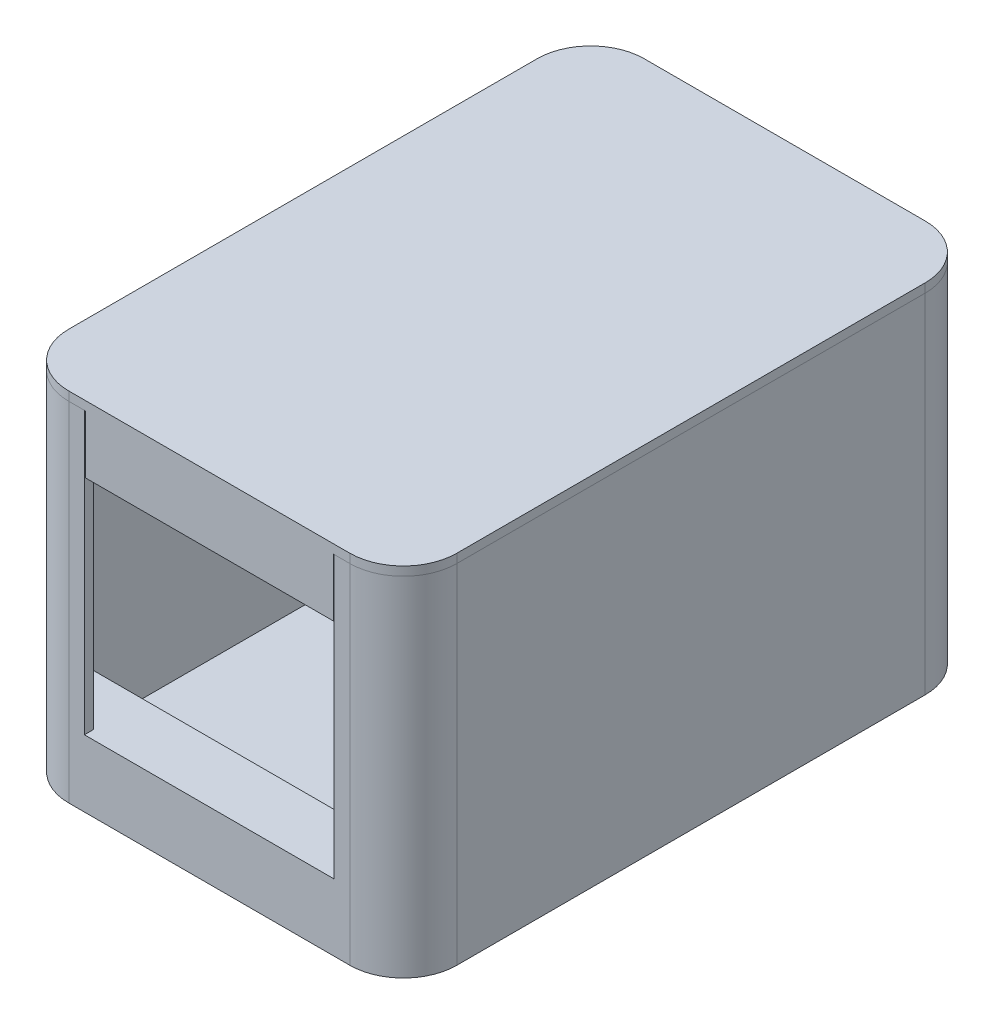
SolidWorks part; units mm, degrees
other "Cover"
other "Case"
ref_plane "Front Plane" through (0, 0, 0) normal (0, 0, 1) x (1, 0, 0)
ref_plane "Top Plane" through (0, 0, 0) normal (0, 1, 0) x (1, 0, 0)
ref_plane "Right Plane" through (0, 0, 0) normal (1, 0, 0) x (0, 0, -1)
sketch "Sketch1" plane through (0, 0, 0) normal (0, 1, 0) x (1, 0, 0)
  line L0 (43.5, 52.5) -> (43.5, -52.5)
  line L1 (-31.5, 62.5) -> (31.5, 62.5) construction
  line L2 (-41.5, 52.5) -> (-41.5, -52.5) construction
  line L3 (-31.5, -62.5) -> (31.5, -62.5) construction
  line L4 (41.5, 52.5) -> (41.5, -52.5) construction
  line L5 (-41.5, 62.5) -> (41.5, -62.5) construction
  line L6 (-41.5, -62.5) -> (41.5, 62.5) construction
  line L7 (-31.5, -64.5) -> (31.5, -64.5)
  line L8 (-43.5, 52.5) -> (-43.5, -52.5)
  line L9 (-31.5, 64.5) -> (31.5, 64.5)
  arc A0 (31.5, -62.5) -> (41.5, -52.5) centre (31.5, -52.5) ccw construction
  arc A1 (-41.5, -52.5) -> (-31.5, -62.5) centre (-31.5, -52.5) ccw construction
  arc A2 (-41.5, 52.5) -> (-31.5, 62.5) centre (-31.5, 52.5) cw construction
  arc A3 (41.5, 52.5) -> (31.5, 62.5) centre (31.5, 52.5) ccw construction
  arc A4 (31.5, -64.5) -> (43.5, -52.5) centre (31.5, -52.5) ccw
  arc A5 (-43.5, -52.5) -> (-31.5, -64.5) centre (-31.5, -52.5) ccw
  arc A6 (-43.5, 52.5) -> (-31.5, 64.5) centre (-31.5, 52.5) cw
  arc A7 (43.5, 52.5) -> (31.5, 64.5) centre (31.5, 52.5) ccw
  point P0 (0, 0)
  dimension "D3" = 10
  dimension "D1" = 125
  dimension "D2" = 83
  dimension "D4" = 2
extrude "Boss-Extrude1" add sketch "Sketch1" along normal blind 80
ref_plane "Plane1" through (0, 78, 0) normal (0, 1, 0) x (1, 0, 0)
split "Split1" trim tools "Plane1" bodies to split 101 resulting bodies 102 103
shell "Shell1" thickness 2
sketch "Sketch2" plane through (0, 2, 0) normal (0, 1, 0) x (1, 0, 0)
  line L0 (0, 51) -> (0, -51) construction
  line L1 (-41.5, 52.5) -> (-41.5, -52.5) construction
  line L2 (41.5, -52.5) -> (41.5, 52.5) construction
  line L3 (-41.5, 52.5) -> (-41.5, -52.5) construction
  line L4 (41.5, -52.5) -> (41.5, 52.5) construction
  line L5 (41.5, -52.5) -> (41.5, 52.5) construction
  line L6 (-41.5, 52.5) -> (41.5, 52.5)
  line L7 (-41.5, 52.5) -> (-41.5, 51)
  line L8 (-41.5, 51) -> (41.5, 51)
  line L9 (41.5, 52.5) -> (41.5, 51)
  line L10 (-41.5, 52.5) -> (41.5, 51) construction
  line L11 (-41.5, 51) -> (41.5, 52.5) construction
  line L12 (-23.284, 0) -> (23.284, 0) construction
  line L13 (31.5, 62.5) -> (-31.5, 62.5) construction
  line L14 (31.5, 62.5) -> (-31.5, 62.5)
  line L19 (-41.5, 52.5) -> (41.5, 52.5)
  line L20 (-41.5, -51) -> (41.5, -52.5) construction
  line L21 (-41.5, -52.5) -> (41.5, -51) construction
  line L22 (-41.5, -52.5) -> (41.5, -52.5)
  line L23 (31.5, -62.5) -> (-31.5, -62.5)
  line L24 (41.5, -52.5) -> (41.5, -51)
  line L25 (-41.5, -51) -> (41.5, -51)
  line L26 (-41.5, -52.5) -> (-41.5, -51)
  line L27 (-41.5, -52.5) -> (41.5, -52.5)
  arc A0 (41.5, 52.5) -> (31.5, 62.5) centre (31.5, 52.5) ccw construction
  arc A1 (-31.5, 62.5) -> (-41.5, 52.5) centre (-31.5, 52.5) ccw construction
  arc A2 (41.5, 52.5) -> (31.5, 62.5) centre (31.5, 52.5) ccw
  arc A3 (-31.5, 62.5) -> (-41.5, 52.5) centre (-31.5, 52.5) ccw
  arc A4 (-31.5, -62.5) -> (-41.5, -52.5) centre (-31.5, -52.5) cw
  arc A5 (41.5, -52.5) -> (31.5, -62.5) centre (31.5, -52.5) cw
  point P4 (0, 0)
  point P9 (0, 51.75)
  point P20 (0, -51.75)
  point P23 (0, 0)
  arc M9 (41.5, 52.5) -> (31.5, 62.5) centre (31.5, 52.5) ccw
  line M10 (31.5, 62.5) -> (-31.5, 62.5)
  arc M11 (-31.5, 62.5) -> (-41.5, 52.5) centre (-31.5, 52.5) ccw
  line M12 (-41.5, 52.5) -> (-41.5, -52.5)
  arc M13 (-41.5, -52.5) -> (-31.5, -62.5) centre (-31.5, -52.5) ccw
  line M14 (-31.5, -62.5) -> (31.5, -62.5)
  arc M15 (31.5, -62.5) -> (41.5, -52.5) centre (31.5, -52.5) ccw
  line M16 (41.5, -52.5) -> (41.5, 52.5)
  dimension "D1" = 102
extrude "Boss-Extrude2" add sketch "Sketch2" along normal blind 13 contours L8 L6 M12 M16 | L6 M11 M9 M10 | L22 M13 M14 M15 | L25 L22 M12 M16
sketch "Sketch4" plane through (0, 78, 0) normal (0, -1, 0) x (1, 0, 0)
  line L0 (-31.5, 62.5) -> (31.5, 62.5) construction
  line L1 (-41.5, -52.5) -> (-41.5, 52.5) construction
  line L2 (31.5, -62.5) -> (-31.5, -62.5) construction
  line L3 (41.5, 52.5) -> (41.5, -52.5) construction
  line L4 (-31.5, 62.5) -> (31.5, 62.5)
  line L5 (-41.5, -52.5) -> (-41.5, 52.5)
  line L6 (31.5, -62.5) -> (-31.5, -62.5)
  line L7 (41.5, 52.5) -> (41.5, -52.5)
  line L8 (39.5, 52.5) -> (39.5, -52.5)
  line L9 (31.5, -60.5) -> (-31.5, -60.5)
  line L10 (-39.5, -52.5) -> (-39.5, 52.5)
  line L11 (-31.5, 60.5) -> (31.5, 60.5)
  line L12 (-31.5, 64.5) -> (31.5, 64.5) construction
  line L13 (-31.5, 64.5) -> (31.5, 64.5) construction
  line L14 (31.5, -64.5) -> (-31.5, -64.5) construction
  line L15 (-27.8, 62.5) -> (27.8, 62.5)
  line L16 (-27.8, 62.5) -> (-27.8, 64.5)
  line L17 (-27.8, 64.5) -> (27.8, 64.5)
  line L18 (27.8, 62.5) -> (27.8, 64.5)
  line L19 (31.5, -64.5) -> (-31.5, -64.5) construction
  line L21 (-27.8, -64.5) -> (27.8, -64.5)
  line L22 (-27.8, -64.5) -> (-27.8, -62.5)
  line L23 (-27.8, -62.5) -> (27.8, -62.5)
  line L24 (27.8, -64.5) -> (27.8, -62.5)
  arc A0 (41.5, 52.5) -> (31.5, 62.5) centre (31.5, 52.5) ccw construction
  arc A1 (-31.5, 62.5) -> (-41.5, 52.5) centre (-31.5, 52.5) ccw construction
  arc A2 (-41.5, -52.5) -> (-31.5, -62.5) centre (-31.5, -52.5) ccw construction
  arc A3 (31.5, -62.5) -> (41.5, -52.5) centre (31.5, -52.5) ccw construction
  arc A4 (41.5, 52.5) -> (31.5, 62.5) centre (31.5, 52.5) ccw
  arc A5 (-31.5, 62.5) -> (-41.5, 52.5) centre (-31.5, 52.5) ccw
  arc A6 (-41.5, -52.5) -> (-31.5, -62.5) centre (-31.5, -52.5) ccw
  arc A7 (31.5, -62.5) -> (41.5, -52.5) centre (31.5, -52.5) ccw
  arc A8 (31.5, -60.5) -> (39.5, -52.5) centre (31.5, -52.5) ccw
  arc A9 (-39.5, -52.5) -> (-31.5, -60.5) centre (-31.5, -52.5) ccw
  arc A10 (-31.5, 60.5) -> (-39.5, 52.5) centre (-31.5, 52.5) ccw
  arc A11 (39.5, 52.5) -> (31.5, 60.5) centre (31.5, 52.5) ccw
  point P30 (0, 64.5)
  point P31 (0, 64.5)
  point P38 (0, -64.5)
  point P39 (0, -64.5)
  line M19 (31.5, 64.5) -> (-31.5, 64.5)
  line M23 (-31.5, -64.5) -> (31.5, -64.5)
  dimension "D2" = 55.6
  dimension "D1" = 2
extrude "Boss-Extrude3" add sketch "Sketch4" along normal blind 13 contours L6 A7 L7 A4 L4 A5 L5 A6 A11 L8 A8 L9 A9 L10 A10 L11 | L4 L18 L16 M19 | L24 L6 L22 M23
chamfer "Chamfer1" distance 1 angle 45 10 edges at (-29.65, 65, -62.5) (-38.5711, 65, -59.5711) (-41.5, 65, 0) (-38.5711, 65, 59.5711) (-29.65, 65, 62.5) (29.65, 65, -62.5) (38.5711, 65, -59.5711) (41.5, 65, 0) (38.5711, 65, 59.5711) (29.65, 65, 62.5)
sketch "Sketch3" plane through (0, 0, 64.5) normal (0, 0, 1) x (1, 0, 0)
  line L0 (-31.5, 0) -> (31.5, 0) construction
  line L1 (-28, 78) -> (28, 78)
  line L2 (-28, 78) -> (-28, 15)
  line L3 (-28, 15) -> (28, 15)
  line L4 (28, 78) -> (28, 15)
  line L5 (-28, 78) -> (28, 15) construction
  line L6 (-28, 15) -> (28, 78) construction
  line L7 (-31.5, 78) -> (31.5, 78) construction
  line L8 (-31.5, 0) -> (31.5, 0) construction
  line L9 (-31.5, 78) -> (31.5, 78) construction
  point P0 (0, 46.5)
  dimension "D1" = 15
  dimension "D2" = 56
extrude "Cut-Extrude1" cut sketch "Sketch3" against normal through all
chamfer "Chamfer2" distance 1 angle 45 10 edges at (-29.75, 78, -62.5) (-38.5711, 78, -59.5711) (-41.5, 78, 0) (-29.75, 78, 62.5) (-38.5711, 78, 59.5711) (29.75, 78, -62.5) (38.5711, 78, -59.5711) (29.75, 78, 62.5) (41.5, 78, 0) (38.5711, 78, 59.5711)
